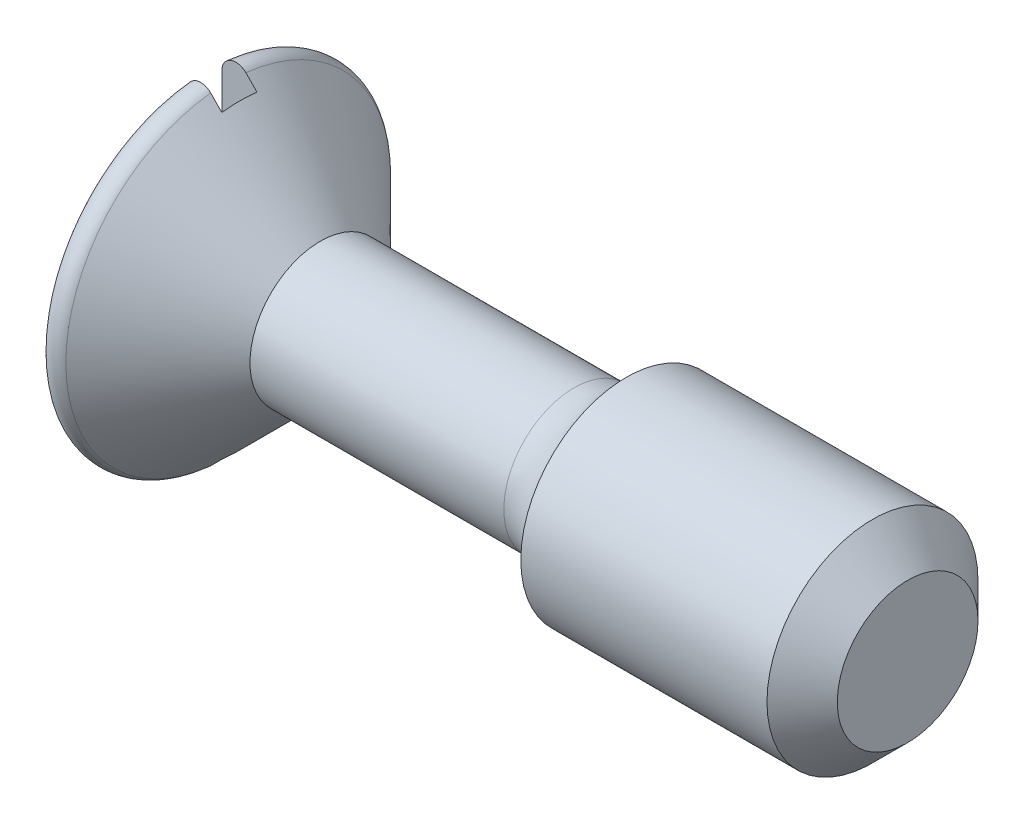
SolidWorks part; units mm, degrees
ref_plane "Front" through (0, 0, 0) normal (0, 0, 1) x (1, 0, 0)
ref_plane "Top" through (0, 0, 0) normal (0, 1, 0) x (1, 0, 0)
ref_plane "Right" through (0, 0, 0) normal (1, 0, 0) x (0, 0, -1)
ref_plane "Plane1" through (1.65, 0, 0) normal (1, 0, 0) x (0, 0, -1)
sketch "Sketch1" plane through (1.65, 0, 0) normal (1, 0, 0) x (0, 0, -1)
  circle A0 centre (0, 0) radius 1
extrude "BaseHead" add sketch "Sketch1" against normal blind 1.65 draft 45 draft outward yes
sketch "Sketch2" plane through (1.65, 0, 0) normal (1, 0, 0) x (0, 0, -1)
  line L0 (0, 0) -> (10, 0) construction
  circle A0 centre (0, 0) radius 1
  circle A1 centre (0, 0) radius 1 construction
  dimension "l" = 10
extrude "BaseBody" add sketch "Sketch2" along normal blind 8.35
sketch "Sketch3" plane through (-1.4, 0, 1.4) normal (0, 1, 0) x (0, 0, -1)
  line L1 (1.15, -1.4) -> (1.65, -1.4)
  line L2 (1.15, -1.4) -> (1.15, -1.9)
  line L3 (1.15, -1.9) -> (1.65, -1.9)
  line L4 (1.65, -1.4) -> (1.65, -1.9)
  dimension "t" = 0.5
  dimension "m" = 0.25
extrude "Slot" cut sketch "Sketch3" against normal through all and the other way through all
sketch "Sketch4" plane through (10, 0.2825, -0.3237) normal (1, 0, 0) x (0, 0, -1)
  circle A0 centre (-0.3237, -0.2825) radius 1.5
  circle A1 centre (-0.3237, -0.2825) radius 1 construction
extrude "BaseEnd" add sketch "Sketch4" against normal blind 4
cosmetic thread "ThreadCosmetic1" [suppressed] parameters "THD_MINOR"=1.75
chamfer "Chamfer1" distance 0.5 angle 45 1 edges at (10, 0, -1.5)
fillet "Fillet" radius 0.8 1 edges at (6, 0, -1)
fillet "Fillet1" radius 0.2 2 edges at (0, 0, 2.65) (0, 0, -2.65)
sketch "Sketch5" plane through (0, 0, 0) normal (0, 0, 1) x (1, 0, 0)
  line L0 (6, 0.9587) -> (6.3125, 1.5)
  line L1 (6.3125, 1.5) -> (6.3125, 2.125)
  line L2 (6.3125, 2.125) -> (5.6875, 2.125)
  line L3 (5.6875, 2.125) -> (5.6875, 1.5)
  line L4 (5.6875, 1.5) -> (6, 0.9587)
  line L5 (0, 0) -> (8.0202, 0) construction
  line L8 (10, -1) -> (10, 1) construction
  dimension "D1" = 3
  dimension "D2" = 0.625
  dimension "D3" = 4
revolve "Cut-Revolve10" [suppressed] cut sketch "Sketch5" angle 360 about L5
pattern_linear "LPattern10" [suppressed] count 5 spacing 0.75 along (1, 0, 0) of bodies 106
equation "\"m@Sketch3\" = \"n@Sketch3\" / 2"
equation "\"D1@Plane1\"=\"k@BaseHead\""
equation "\"l@BaseBody\" = \"l@Sketch2\" - \"k@BaseHead\""
equation "\"D1@Sketch5\" = \"d@Sketch4\""
equation "\"D2@Sketch5\" =  ( \"d@Sketch4\" - \"THD_MINOR@ThreadCosmetic1\" )  / 2"
equation "\"D3@LPattern10\" = \"D2@Sketch5\" * 1.2"
equation "\"D1@LPattern10\" = \"b@BaseEnd\" / \"D3@LPattern10\""
equation "\"D3@Sketch5\" = \"b@BaseEnd\""
